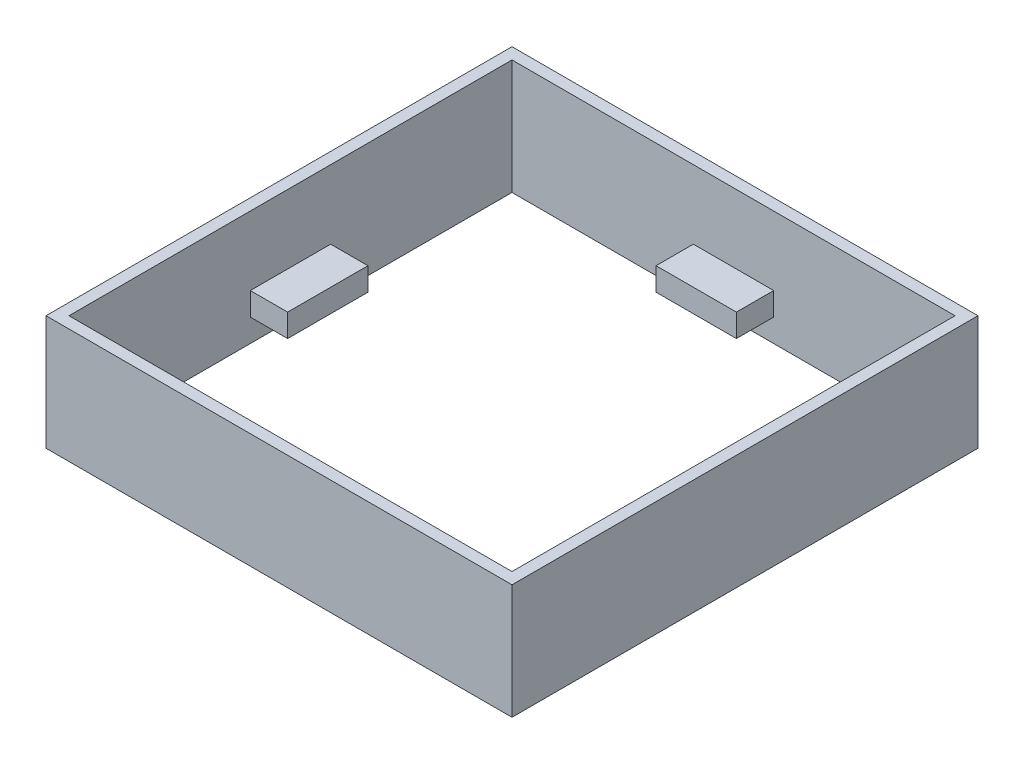
SolidWorks part; units mm, degrees
ref_plane "Front Plane" through (0, 0, 0) normal (0, 0, 1) x (1, 0, 0)
ref_plane "Top Plane" through (0, 0, 0) normal (0, 1, 0) x (1, 0, 0)
ref_plane "Right Plane" through (0, 0, 0) normal (1, 0, 0) x (0, 0, -1)
sketch "Sketch1" plane through (0, 0, 0) normal (0, 1, 0) x (1, 0, 0)
  line L8 (38.1, 38.1) -> (-38.1, -38.1) construction
  line L9 (38.1, -38.1) -> (-38.1, 38.1) construction
  line L10 (38.1, -38.1) -> (-38.1, -38.1) construction
  line L11 (38.1, -38.1) -> (38.1, 38.1) construction
  line L12 (-38.1, -38.1) -> (-38.1, 38.1) construction
  line L13 (38.1, 38.1) -> (-38.1, 38.1) construction
  line L14 (38.1, 38.1) -> (-38.1, -38.1)
  line L15 (38.1, -38.1) -> (-38.1, 38.1)
  line L16 (38.1, -38.1) -> (-38.1, -38.1)
  line L17 (38.1, -38.1) -> (38.1, 38.1)
  line L18 (-38.1, -38.1) -> (-38.1, 38.1)
  line L19 (38.1, 38.1) -> (-38.1, 38.1)
sketch "Sketch6" plane through (0, 0, 0) normal (0, 0, 1) x (1, 0, 0)
  line L0 (0, 0) -> (0, -23.6993) construction
sketch "Sketch4" plane through (0, 0, 0) normal (0, 1, 0) x (1, 0, 0)
  line L10 (40.6, 40.6) -> (-40.6, 40.6)
  line L11 (-40.6, 40.6) -> (-40.6, -40.6)
  line L12 (-40.6, -40.6) -> (40.6, -40.6)
  line L13 (40.6, -40.6) -> (40.6, 40.6)
  line L14 (-38.6, -38.6) -> (38.6, -38.6)
  line L15 (38.6, -38.6) -> (38.6, 38.6)
  line L16 (-38.6, 38.6) -> (-38.6, -38.6)
  line L17 (38.6, 38.6) -> (-38.6, 38.6)
  line L18 (-38.6, -38.6) -> (38.6, -38.6)
  line L19 (38.6, -38.6) -> (38.6, 38.6)
  line L20 (-38.6, 38.6) -> (-38.6, -38.6)
  line L21 (38.6, 38.6) -> (-38.6, 38.6)
  dimension "D1" = 0.5
  dimension "D2" = 2
extrude "Boss-Extrude1" add sketch "Sketch4" against normal blind 20
sketch "Sketch5" plane through (0, -20, 0) normal (0, -1, 0) x (1, 0, 0)
  line L0 (-38.6, -38.6) -> (-38.6, 38.6) construction
  line L2 (-38.6, 7) -> (-32.1, 7)
  line L3 (-38.6, 7) -> (-38.6, -7)
  line L4 (-38.6, -7) -> (-32.1, -7)
  line L5 (-32.1, 7) -> (-32.1, -7)
  line L6 (-36.6, 5) -> (-33.6, 5)
  line L7 (-36.6, 5) -> (-36.6, -5)
  line L8 (-36.6, -5) -> (-33.6, -5)
  line L9 (-33.6, 5) -> (-33.6, -5)
  point P6 (-38.6, 0)
  point P7 (-36.6, 0)
  point P8 (-38.6, 0)
  point P13 (-32.1, 0)
  dimension "D1" = 3
  dimension "D2" = 10
  dimension "D3" = 2
  dimension "D4" = 1.5
  dimension "D5" = 2
extrude "Boss-Extrude2" add sketch "Sketch5" against normal blind 4 from offset 4 contours L5 L4 L3 L2 offset against normal yes
extrude "Cut-Extrude2" cut sketch "Sketch5<3>" against normal blind 2 from offset 5 contours L7 L8 L9 L6 offset against normal yes
sketch "Sketch5<3>" plane through (0, -20, 0) normal (0, -1, 0) x (1, 0, 0) same geometry as "Sketch5"
pattern_circular "CirPattern2" count 4 over 360 about axis through (0, 0, 0) along (0, -1, 0) of "Boss-Extrude2", "Cut-Extrude2"
